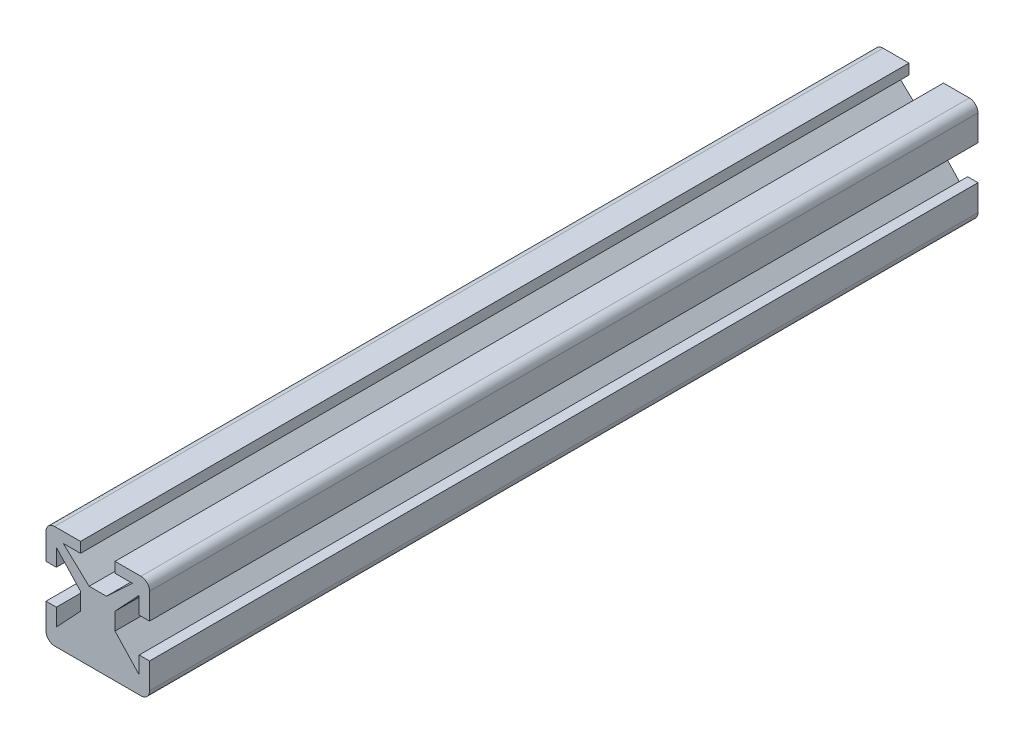
SolidWorks part; units mm, degrees
ref_plane "Plan de face" through (0, 0, 0) normal (0, 0, 1) x (1, 0, 0)
ref_plane "Plan de dessus" through (0, 0, 0) normal (0, 1, 0) x (1, 0, 0)
ref_plane "Plan de droite" through (0, 0, 0) normal (1, 0, 0) x (0, 0, -1)
sketch "Esquisse1" plane through (0, 0, 0) normal (0, 0, 1) x (1, 0, 0)
  line L0 (-6, 5) -> (-6, -5)
  line L1 (-5, 6) -> (5, 6)
  line L2 (-5, -6) -> (5, -6)
  line L3 (6, 5) -> (6, -5)
  line L4 (-5, 5) -> (5, -5) construction
  line L5 (5, 5) -> (-5, -5) construction
  arc A0 (-5, 6) -> (-6, 5) centre (-5, 5) ccw
  arc A1 (5, 6) -> (6, 5) centre (5, 5) cw
  arc A2 (6, -5) -> (5, -6) centre (5, -5) cw
  arc A3 (-5, -6) -> (-6, -5) centre (-5, -5) cw
  point P12 (0, 0)
  dimension "D1" = 1
  dimension "D2" = 1
  dimension "D4" = 1
  dimension "D3" = 12
extrude "Extrusion1" add sketch "Esquisse1" along normal mid plane 96
sketch "Esquisse3" plane through (0, 0, 48) normal (0, 0, 1) x (1, 0, 0)
  line L0 (6, 2) -> (4.8, 2)
  line L2 (4.8, 2) -> (4.8, 4)
  line L3 (2, 1) -> (2, -1)
  line L4 (4.8, -4) -> (4.8, -2)
  line L5 (4.8, -2) -> (6, -2)
  line L6 (6, -5) -> (6, 5) construction
  line L7 (4.8, 4) -> (2, 1)
  line L8 (6, 2) -> (6, -2)
  line L9 (4.8, -4) -> (2, -1)
  point P4 (6, 0)
  point P10 (6, 0)
  dimension "D1" = 4
  dimension "D2" = 1.2
  dimension "D3" = 4
  dimension "D4" = 2
  dimension "D5" = 2
extrude "Enlèv. mat.-Extru.1" cut sketch "Esquisse3" against normal through all
ref_axis "Axe1" through (0, 0, -1) along (0, 0, 1)
pattern_circular "Répétition circulaire1" count 3 every 90 about axis through (0, 0, -1) along (0, 0, 1) of "Enlèv. mat.-Extru.1"
